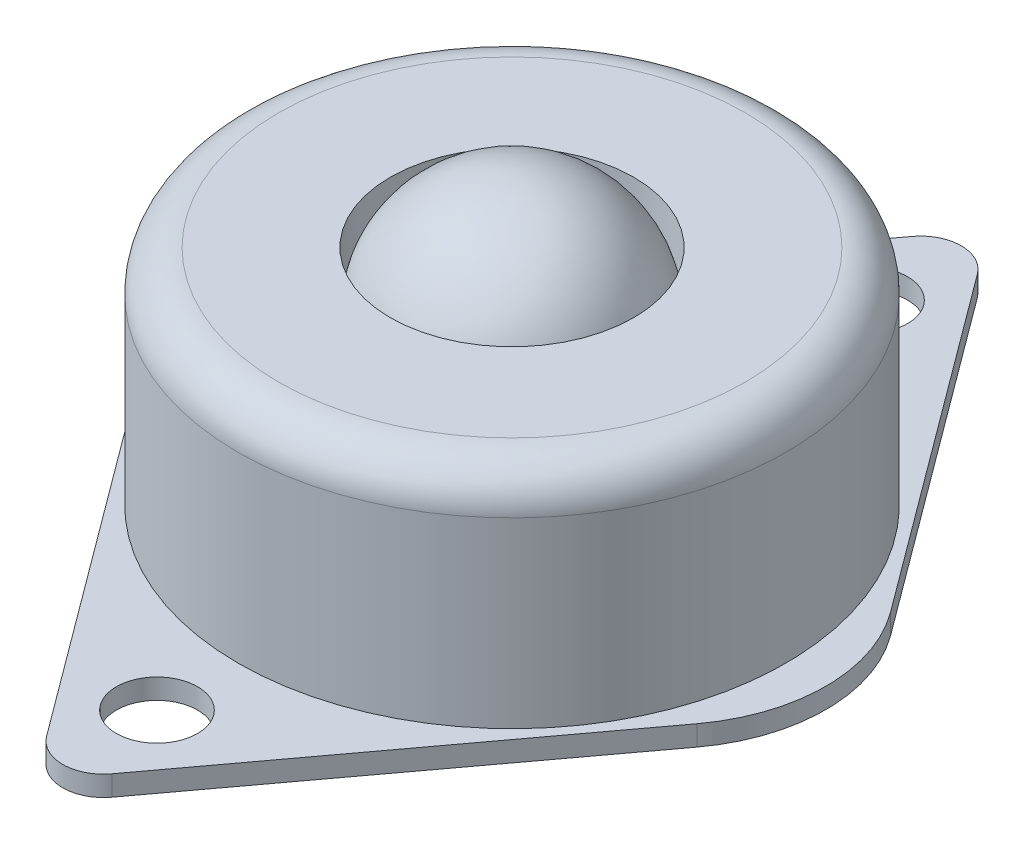
SolidWorks part; units mm, degrees
ref_plane "前视基准面" through (0, 0, 0) normal (0, 0, 1) x (1, 0, 0)
ref_plane "上视基准面" through (0, 0, 0) normal (0, 1, 0) x (1, 0, 0)
ref_plane "右视基准面" through (0, 0, 0) normal (1, 0, 0) x (0, 0, -1)
sketch "草图1" plane through (0, 0, 0) normal (0, 1, 0) x (1, 0, 0)
  line L0 (0, 28.2203) -> (0, -28.2203) construction
  line L1 (-22.7733, 0) -> (38.1873, 0) construction
  line L2 (-1.6063, 21.3343) -> (-13.8958, 4.766)
  line L3 (-13.8958, -4.766) -> (-1.6063, -21.3343)
  line L4 (13.8958, -4.766) -> (1.6063, -21.3343)
  line L5 (1.6063, 21.3343) -> (13.8958, 4.766)
  circle A0 centre (0, 0) radius 14
  circle A1 centre (0, 17.5) radius 2
  circle A2 centre (0, -17.5) radius 2
  arc A3 (1.6063, 21.3343) -> (-1.6063, 21.3343) centre (0, 20.1429) ccw
  arc A4 (-1.6063, -21.3343) -> (1.6063, -21.3343) centre (0, -20.1429) ccw
  arc A5 (-13.8958, 4.766) -> (-13.8958, -4.766) centre (-7.4704, 0) ccw
  arc A6 (13.8958, -4.766) -> (13.8958, 4.766) centre (7.4704, 0) ccw
  point P17 (0, 23.5)
  point P20 (0, -23.5)
  point P23 (-17.4308, 0)
  point P26 (17.4308, 0)
  dimension "D1" = 28
  dimension "D2" = 4
  dimension "D3" = 35
  dimension "D5" = 2
  dimension "D6" = 2
  dimension "D7" = 8
  dimension "D8" = 8
  dimension "D4" = 47
extrude "凸台-拉伸1" add sketch "草图1" along normal blind 1 contours L5 A3 L2 A0 A1 | A0 | L4 A6 L5 A0 | L3 A4 L4 A0 A2 | L2 A5 L3 A0 region at (0, 0, -21.879) region at (-14.2194, 0, 0) region at (0, 0, 0) region at (14.2194, 0, 0) region at (0, 0, 14.2639)
sketch "草图2" plane through (0, 1, 0) normal (0, 1, 0) x (1, 0, 0)
  line L4 (13.8958, 4.766) -> (1.6063, 21.3343)
  line L5 (-1.6063, 21.3343) -> (-13.8958, 4.766)
  line L6 (-13.8958, -4.766) -> (-1.6063, -21.3343)
  line L7 (1.6063, -21.3343) -> (13.8958, -4.766)
  line L8 (13.8958, 4.766) -> (1.6063, 21.3343)
  line L9 (-1.6063, 21.3343) -> (-13.8958, 4.766)
  line L10 (-13.8958, -4.766) -> (-1.6063, -21.3343)
  line L11 (1.6063, -21.3343) -> (13.8958, -4.766)
  circle A0 centre (0, 0) radius 13.5
  circle A1 centre (0, 0) radius 6
  arc A4 (1.6063, 21.3343) -> (-1.6063, 21.3343) centre (0, 20.1429) ccw
  arc A5 (-13.8958, 4.766) -> (-13.8958, -4.766) centre (-7.4704, 0) ccw
  arc A6 (-1.6063, -21.3343) -> (1.6063, -21.3343) centre (0, -20.1429) ccw
  arc A7 (13.8958, -4.766) -> (13.8958, 4.766) centre (7.4704, 0) ccw
  arc A8 (1.6063, 21.3343) -> (-1.6063, 21.3343) centre (0, 20.1429) ccw
  arc A9 (-13.8958, 4.766) -> (-13.8958, -4.766) centre (-7.4704, 0) ccw
  arc A10 (-1.6063, -21.3343) -> (1.6063, -21.3343) centre (0, -20.1429) ccw
  arc A11 (13.8958, -4.766) -> (13.8958, 4.766) centre (7.4704, 0) ccw
  dimension "D2" = 27
  dimension "D3" = 12
  dimension "D1" = 0
extrude "凸台-拉伸2" add sketch "草图2" along normal blind 11 contours A0 region at (-13.1182, 1, 0)
fillet "圆角1" radius 2 1 edges at (0, 12, 13.5) type face fillet first side face at (0, 12, 6) second side face at (0, 12, 13.5)
ref_plane "基准面1" through (0, 9, 0) normal (0, 1, 0) x (1, 0, 0)
sketch "草图5" plane through (0, 9, 0) normal (0, 1, 0) x (1, 0, 0)
  line L0 (6, 0) -> (-6, 0)
  circle A0 centre (0, 0) radius 6
  circle A1 centre (0, 0) radius 6
  circle A2 centre (0, 0) radius 6
  dimension "D1" = 0
revolve "旋转3" add sketch "草图5" angle 360 about L0 region at (0, 9, -2.5465) reverse direction yes
